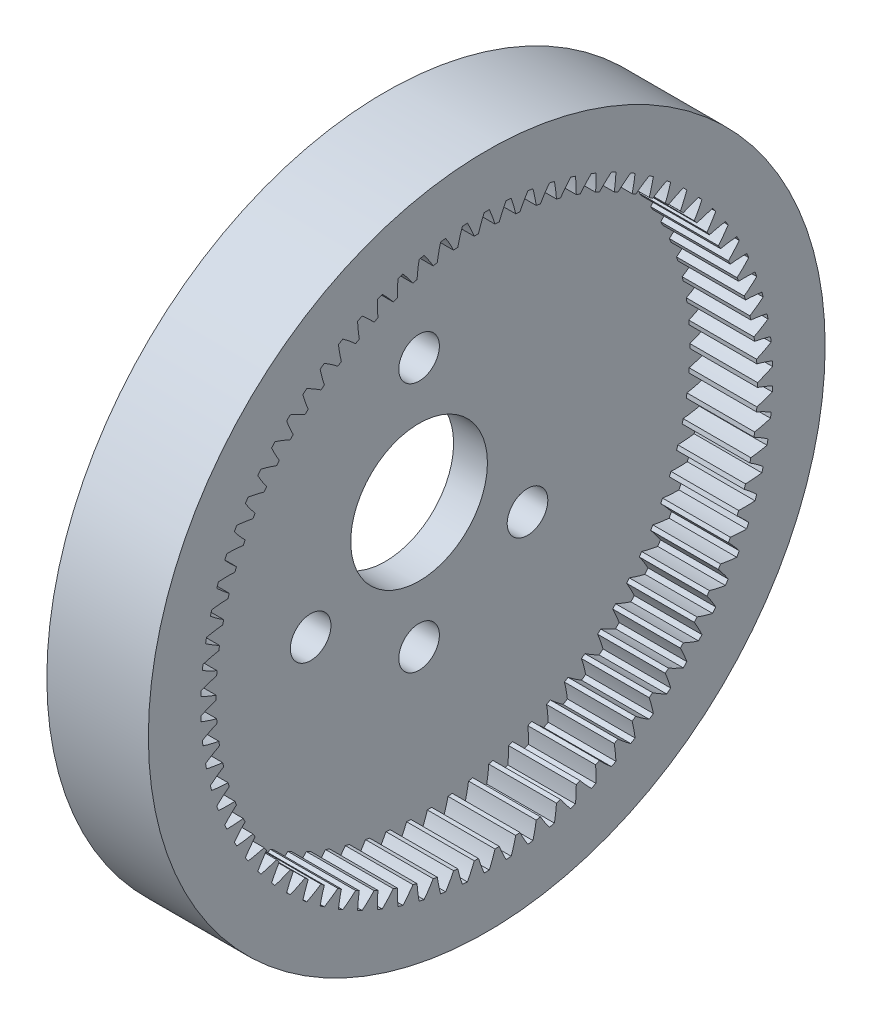
SolidWorks part; units mm, degrees
ref_plane "Plane1" through (0, 0, 0) normal (0, 0, 1) x (1, 0, 0)
ref_plane "Plane2" through (0, 0, 0) normal (0, 1, 0) x (1, 0, 0)
ref_plane "Plane3" through (0, 0, 0) normal (1, 0, 0) x (0, 0, -1)
other "Configuration Table"
sketch "HoldingSke" plane through (0, 0, 0) normal (0, 1, 0) x (1, 0, 0)
  line L0 (0, 0) -> (0.2783, -1.9805)
  line L1 (-15, 0) -> (100, 0) construction
  line L2 (0, 0) -> (-2.1039, 2.3779)
  line L3 (0, 0) -> (-11.863, 4.5341)
  line L4 (0, 0) -> (1.2019, 8.552)
  line L5 (0, 0) -> (-23.7986, -8.8762)
  line L6 (0, 0) -> (-10.5278, -7.1032)
  line L7 (-2.1039, 2.3779) -> (3.3635, 27.1825)
  line L8 (-76.2, 2.8779) -> (-54.61, 2.8779)
  line L9 (-71.009, 38.7566) -> (-53.1078, 45.2721)
  line L10 (-76.2, 71.12) -> (104.1128, 71.12)
  line L11 (0, 0) -> (-12, 0)
  line L12 (-76.2, 101.6) -> (-76.181, 101.6)
  line L13 (24.9733, 27.94) -> (52.9518, 28.4284)
  line L14 (24.9733, 27.94) -> (24.9743, 27.94)
  line L15 (24.9733, 27.94) -> (100.4006, 29.5858)
  circle A0 centre (0, 0) radius 25
  circle A1 centre (0, 0) radius 12.7
  circle A2 centre (0, 0) radius 12.7
  dimension "MHD" = 25.4
  dimension "Hub_dia" = 25.4
  dimension "Diameter" = 50
  dimension "Num_teeth" = 82
  dimension "Pitch" = 2
  dimension "Overall_len" = 25.4
  dimension "Show_teeth" = 82
  dimension "Thickness" = 12.7
  dimension "OAL" = 25.4001
  dimension "T_dim" = 21.59
  dimension "Ap" = 20
  dimension "H" = 19.05
  dimension "Pitch_radius" = 180.3128
  dimension "Width" = 12
  dimension "Backlash" = 0.019
  dimension "Addendum_fac" = 1
  dimension "Dedendum_fac" = 1.25
  dimension "Clearance_fac" = 0.25
  dimension "Dedendum_add" = 0.001
  dimension "Module" = 0.5
sketch "BasProSke" plane through (0, 0, 0) normal (0, 1, 0) x (1, 0, 0)
  line L0 (-10, 0) -> (60, 0) construction
  line L1 (0, 20) -> (0, 25)
  line L2 (0, 20) -> (12, 20)
  line L3 (12, 20) -> (12, 25)
  line L4 (12, 25) -> (0, 25)
  dimension "Diameter" = 50
  dimension "Thickness" = 12
  dimension "Inside_diameter" = 40
revolve "Base-Revolve" add sketch "BasProSke" angle 360 about L0
sketch "TooCutSke" plane through (0, 0, 0) normal (1, 0, 0) x (0, 0, -1)
  line L3 (0.4402, 20.4953) -> (0.4402, 53.6633) construction
  line L4 (0, 0) -> (0, 59.563) construction
  line L5 (0, 0) -> (-2.6171, 68.2774) construction
  line L6 (-9.1946, 16.9976) -> (37.151, 18.7741) construction
  circle A0 centre (0, 0) radius 20.5 construction
  circle A1 centre (0, 0) radius 21.126 construction
  circle A2 centre (0, 0) radius 17.3373 construction
  circle A3 centre (0, 0) radius 19.9746 construction
  arc A4 (0.6164, 19.9651) -> (0.1876, 21.1252) centre (-9.1946, 16.9976) ccw
  arc A5 (0.6164, 19.9651) -> (-0.6164, 19.9651) centre (0, 0) ccw
  arc A6 (0.1876, 21.1252) -> (-0.1876, 21.1252) centre (0, 0) ccw
  arc A7 (-0.1876, 21.1252) -> (-0.6164, 19.9651) centre (9.1946, 16.9976) ccw
  dimension "Pitch_dia" = 41
  dimension "Base_dia" = 34.6747
  dimension "Root_dia" = 42.252
  dimension "Overcut_dia" = 39.9492
  dimension "Flank_rad" = 10.25
  dimension "Half_ang" = 2.195
  dimension "Half_CT" = 0.4402
extrude "ToothCut" cut sketch "TooCutSke" along normal through all
fillet "Breaks" [suppressed] radius 0.05
fillet "RootFillets" [suppressed] radius 0.126
pattern_circular "TeethCuts" count 82 over 360 about axis through (-10, 0, 0) along (1, 0, 0) of "RootFillets", "Breaks", "ToothCut"
sketch "Sketch2" plane through (0, 0, 0) normal (-1, 0, 0) x (0, 0, 1)
  circle A0 centre (0, 0) radius 25
extrude "Boss-Extrude1" add sketch "Sketch2" along normal blind 2.5
sketch "Sketch3" plane through (-2.5, 0, 0) normal (-1, 0, 0) x (0, 0, 1)
  line L0 (0, -9.25) -> (0, 9.25) construction
  line L1 (-8.0107, -4.625) -> (0, 0) construction
  line L2 (0, 0) -> (8.0107, -4.625) construction
  circle A0 centre (0, 0) radius 9.25 construction
  circle A1 centre (0, 0) radius 5.05
  circle A2 centre (0, 9.25) radius 1.5
  circle A3 centre (0, -9.25) radius 1.5
  circle A4 centre (8.0107, -4.625) radius 1.5
  circle A5 centre (-8.0107, -4.625) radius 1.5
  dimension "D1" = 18.5
  dimension "D2" = 10.1
  dimension "D3" = 3
  dimension "D4" = 60
  dimension "D5" = 60
extrude "Cut-Extrude1" cut sketch "Sketch3" against normal blind 2.5 and the other way through all
sketch "Sketch4" plane through (12, 0, 0) normal (1, 0, 0) x (0, 0, -1)
  circle A0 centre (0, 0) radius 25
extrude "Cut-Extrude2" cut sketch "Sketch4" against normal blind 7
equation "' \"Module@HoldingSke\" = 6.35"
equation "' \"Num_teeth@HoldingSke\" = 24"
equation "' \"Ap@HoldingSke\" =  14.5"
equation "' \"Ap@HoldingSke\" = 14.5"
equation "' \"Width@HoldingSke\" = 12"
equation "' \"Diameter@HoldingSke\" = 8 * 25.4"
equation "' \"Show_teeth@HoldingSke\" = 100"
equation "' \"Backlash@HoldingSke\" = 0.009 * 25.4"
equation "' \"Addendum_fac@HoldingSke\" = 1.0"
equation "' \"Dedendum_fac@HoldingSke\" = 1.25"
equation "' \"Dedendum_add@HoldingSke\" = 0.00005 * 25.4"
equation "' \"Clearance_fac@HoldingSke\" = 0.25"
equation "\"Pitch@HoldingSke\" = 1 / \"Module@HoldingSke\" "
equation "\"Overcut_dia@TooCutSke\" = (\"Num_teeth@HoldingSke\" - 2 * \"Addendum_fac@HoldingSke\") / \"Pitch@HoldingSke\" - 0.002 * 25.4"
equation "\"Pitch_dia@TooCutSke\" = \"Num_teeth@HoldingSke\" / \"Pitch@HoldingSke\""
equation "\"Base_dia@TooCutSke\" = \"Num_teeth@HoldingSke\" / \"Pitch@HoldingSke\" * cos((\"Ap@HoldingSke\"  * 3.14159265 / 180)) * 0.90"
equation "\"Root_dia@TooCutSke\" = \"Num_teeth@HoldingSke\"  / \"Pitch@HoldingSke\" + 2 *  \"Dedendum_fac@HoldingSke\"/ \"Pitch@HoldingSke\" + \"Dedendum_add@HoldingSke\" * 2"
equation "\"Half_ang@TooCutSke\" = 180 / \"Num_teeth@HoldingSke\""
equation "\"Half_CT@TooCutSke\" = \"Num_teeth@HoldingSke\" / \"Pitch@HoldingSke\" * sin((3.14159265 / 2 / \"Num_teeth@HoldingSke\")) / 2 + 10 * \"Backlash@HoldingSke\" / 4"
equation "\"Flank_rad@TooCutSke\" = \"Num_teeth@HoldingSke\" / \"Pitch@HoldingSke\" / 4"
equation "\"Radius@RootFillets\"= \"Clearance_fac@HoldingSke\" / \"Pitch@HoldingSke\" + \"Dedendum_add@HoldingSke\""
equation "\"Break_rad@Breaks\" = 0.02 / \"Pitch@HoldingSke\" * 5"
equation "\"Num_teeth@TeethCuts\" = int( \"Show_teeth@HoldingSke\" ) + 1"
equation "\"Num_teeth@TeethCuts\" = ((sgn( \"Num_teeth@TeethCuts\" - \"Num_teeth@HoldingSke\" )-1)*( \"Num_teeth@TeethCuts\" - \"Num_teeth@HoldingSke\" ))/-2+ \"Num_teeth@HoldingSke\""
equation "\"Num_teeth@TeethCuts\" = ((sgn( \"Num_teeth@TeethCuts\" - 2.0)+1)*( \"Num_teeth@TeethCuts\" - 2.0))/2 +2.0"
equation "\"Angle@TeethCuts\" = 360.0 / \"Num_teeth@HoldingSke\""
equation "\"Diameter@BasProSke\" = \"Num_teeth@HoldingSke\"  / \"Pitch@HoldingSke\" + 2 *  \"Dedendum_fac@HoldingSke\"/ \"Pitch@HoldingSke\" + \"Dedendum_add@HoldingSke\" * 2 + 0.002 * 25.4"
equation "\"Diameter@BasProSke\" = ((sgn( \"Diameter@BasProSke\"  - \"Diameter@HoldingSke\" )+1)*( \"Diameter@BasProSke\"  - \"Diameter@HoldingSke\" ))/2 + \"Diameter@HoldingSke\""
equation "\"Inside_diameter@BasProSke\" =  (\"Num_teeth@HoldingSke\" - 2 * \"Addendum_fac@HoldingSke\") / \"Pitch@HoldingSke\" "
equation "\"Thickness@BasProSke\"  = \"Width@HoldingSke\""
